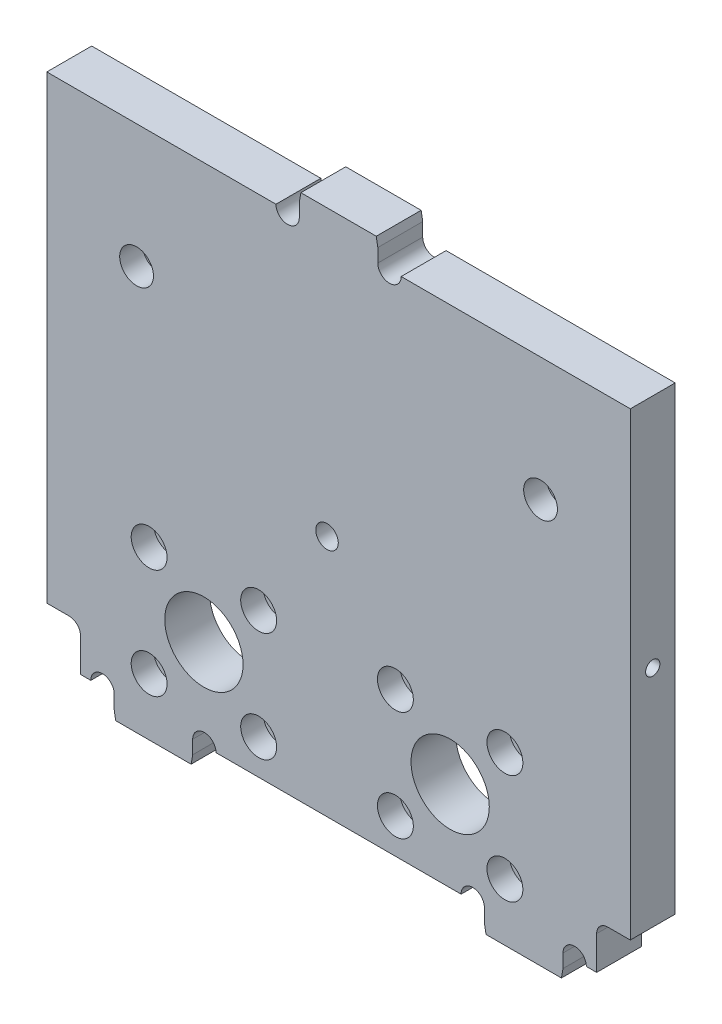
SolidWorks part; units mm, degrees
material "PE High Density"
ref_plane "Front Plane" through (0, 0, 0) normal (0, 0, 1) x (1, 0, 0)
ref_plane "Top Plane" through (0, 0, 0) normal (0, 1, 0) x (1, 0, 0)
ref_plane "Right Plane" through (0, 0, 0) normal (1, 0, 0) x (0, 0, -1)
sketch "Sketch1" plane through (0, 0, 0) normal (0, 0, 1) x (1, 0, 0)
  line L1 (-82.55, -71.4375) -> (82.55, -71.4375)
  line L2 (-82.55, -71.4375) -> (-82.55, 71.4375)
  line L3 (-82.55, 71.4375) -> (82.55, 71.4375)
  line L4 (82.55, -71.4375) -> (82.55, 71.4375)
  line L5 (-82.55, -71.4375) -> (82.55, 71.4375) construction
  line L6 (-82.55, 71.4375) -> (82.55, -71.4375) construction
  point P0 (0, 0)
  dimension "D1" = 165.1
  dimension "D2" = 142.875
extrude "Boss-Extrude1" add sketch "Sketch1" along normal blind 12.7
sketch "Sketch2" plane through (0, 0, 12.7) normal (0, 0, 1) x (1, 0, 0)
  line L0 (82.55, 71.4375) -> (-82.55, 71.4375) construction
  line L1 (-11.1125, 71.4375) -> (11.1125, 71.4375)
  line L2 (-11.1125, 71.4375) -> (-11.1125, 75.2475)
  line L3 (-10.6646, 77.7875) -> (10.6646, 77.7875)
  line L4 (11.1125, 71.4375) -> (11.1125, 75.2475)
  line L5 (10.6646, 77.7875) -> (11.1125, 75.2475)
  line L6 (-10.6646, 77.7875) -> (-11.1125, 75.2475)
  line L7 (82.55, -71.4375) -> (82.55, 71.4375) construction
  point P6 (0, 77.7875)
  dimension "D3" = 170
  dimension "D4" = 170
  dimension "D5" = 3.81
  dimension "D1" = 71.4375
  dimension "D2" = 6.35
extrude "Boss-Extrude2" add sketch "Sketch2" against normal up to surface (12.7 mm away) up to face at (0, 0, 0)
sketch "Sketch4" plane through (0, 0, 12.7) normal (0, 0, 1) x (1, 0, 0)
  line L0 (-11.1125, 71.4375) -> (-82.55, 71.4375) construction
  line L1 (-11.1125, 75.2475) -> (-11.1125, 71.4375) construction
  line L2 (-82.55, 71.4375) -> (82.55, 71.4375) construction
  line L3 (0, 77.7875) -> (0, 0) construction
  line L4 (10.6646, 77.7875) -> (-10.6646, 77.7875) construction
  line L5 (-17.7165, 71.4375) -> (-11.1125, 71.4375)
  line L6 (11.1125, 71.4375) -> (17.7165, 71.4375)
  arc A0 (-17.7165, 71.4375) -> (-11.1125, 71.4375) centre (-14.4145, 71.4375) ccw
  arc A1 (17.7165, 71.4375) -> (11.1125, 71.4375) centre (14.4145, 71.4375) cw
  dimension "D1" = 6.604
  dimension "D2" = 3.302
extrude "Cut-Extrude1" cut sketch "Sketch4" against normal up to next contours A1 L6 | A0 L5
sketch "Sketch5" plane through (0, 0, 12.7) normal (0, 0, 1) x (1, 0, 0)
  line L0 (-82.55, -71.4375) -> (82.55, -71.4375) construction
  line L1 (63.5, -71.4375) -> (41.275, -71.4375)
  line L2 (63.5, -71.4375) -> (63.5, -75.2475)
  line L3 (63.0521, -77.7875) -> (41.7229, -77.7875)
  line L4 (41.275, -71.4375) -> (41.275, -75.2475)
  line L5 (82.55, -71.4375) -> (82.55, 71.4375) construction
  line L6 (41.275, -75.2475) -> (41.7229, -77.7875)
  line L7 (63.5, -75.2475) -> (63.0521, -77.7875)
  dimension "D1" = 22.225
  dimension "D2" = 6.35
  dimension "D3" = 19.05
  dimension "D4" = 170
  dimension "D5" = 170
  dimension "D6" = 3.81
extrude "Boss-Extrude3" add sketch "Sketch5" against normal up to surface (12.7 mm away) up to face at (0, 48.768, 0)
hole_wizard "#21 (0.159) Diameter Hole2" positions "Sketch32" profile "Sketch33" hole size "#21" standard "ANSI Inch"
sketch "Sketch32" plane through (82.55, 0, 0) normal (1, 0, 0) x (0, 0, -1)
  line L0 (-12.7, -71.4375) -> (0, -71.4375) construction
  point P0 (-6.35, 4.7625)
  point P5 (-6.35, -71.4375)
  dimension "D1" = 76.2
sketch "Sketch33" plane through (82.55, 4.7625, 6.35) normal (0, 1, 0) x (0, 0, -1)
  line L0 (0, 0) -> (0, 23.4383)
  line L1 (0, 23.4383) -> (2.0193, 22.225)
  line L2 (2.0193, 22.225) -> (2.0193, 0)
  line L5 (2.0193, 0) -> (0, 0)
  line L10 (0, 23.4383) -> (-2.0193, 22.225) construction
  line L11 (0, -6.35) -> (0, 107.95) construction
  dimension "Hole Dia." = 4.0386
  dimension "Hole Depth" = 22.225
  dimension "Drill Angle" = 118
hole_wizard "#21 (0.159) Diameter Hole3" positions "Sketch34" profile "Sketch35" hole size "#21" standard "ANSI Inch"
sketch "Sketch34" plane through (-82.55, 0, 0) normal (-1, 0, 0) x (0, 0, 1)
  point P0 (6.35, 4.7625)
sketch "Sketch35" plane through (-82.55, 4.7625, 6.35) normal (0, 1, 0) x (0, 0, 1)
  line L0 (0, 0) -> (0, 23.4383)
  line L1 (0, 23.4383) -> (2.0193, 22.225)
  line L2 (2.0193, 22.225) -> (2.0193, 0)
  line L5 (2.0193, 0) -> (0, 0)
  line L10 (0, 23.4383) -> (-2.0193, 22.225) construction
  line L11 (0, -6.35) -> (0, 107.95) construction
  dimension "Hole Dia." = 4.0386
  dimension "Hole Depth" = 22.225
  dimension "Drill Angle" = 118
sketch "Sketch6" plane through (0, 0, 12.7) normal (0, 0, 1) x (1, 0, 0)
  line L0 (-82.55, -71.4375) -> (41.275, -71.4375) construction
  line L1 (82.55, -71.4375) -> (0, -71.4375) construction
  line L2 (34.671, -71.4375) -> (41.275, -71.4375)
  line L3 (52.3875, -77.7875) -> (52.3875, 71.4375) construction
  line L4 (41.7229, -77.7875) -> (63.0521, -77.7875) construction
  line L5 (82.55, 71.4375) -> (17.7165, 71.4375) construction
  line L6 (63.5, -71.4375) -> (70.104, -71.4375)
  arc A0 (41.275, -71.4375) -> (34.671, -71.4375) centre (37.973, -71.4375) ccw
  arc A1 (63.5, -71.4375) -> (70.104, -71.4375) centre (66.802, -71.4375) cw
  dimension "D1" = 6.604
  dimension "D2" = 3.302
extrude "Cut-Extrude2" cut sketch "Sketch6" against normal up to surface (12.7 mm away) up to face at (17.4625, 7.5706, 0)
mirror "Mirror1" about plane through (0, 0, 0) normal (1, 0, 0) of "Boss-Extrude3", "Cut-Extrude2"
sketch "Sketch21" plane through (0, 0, 12.7) normal (0, 0, 1) x (1, 0, 0)
  line L1 (-82.55, 71.4375) -> (-82.55, -71.4375) construction
  line L2 (-34.671, -71.4375) -> (34.671, -71.4375) construction
  line L3 (-82.55, -71.4375) -> (-70.104, -71.4375) construction
  line L4 (-53.594, -30.5435) -> (-22.606, -30.5435) construction
  line L5 (-53.594, -30.5435) -> (-53.594, -61.5315) construction
  line L6 (-53.594, -61.5315) -> (-22.606, -61.5315) construction
  line L7 (-22.606, -30.5435) -> (-22.606, -61.5315) construction
  line L8 (16.0799, -30.5435) -> (47.0679, -30.5435) construction
  line L9 (16.0799, -30.5435) -> (16.0799, -61.5315) construction
  line L10 (16.0799, -61.5315) -> (47.0679, -61.5315) construction
  line L11 (47.0679, -30.5435) -> (47.0679, -61.5315) construction
  circle A0 centre (-57.15, 36.5125) radius 4.7752
  circle A1 centre (57.15, 36.5125) radius 4.7752
  circle A2 centre (-57.15, 36.5125) radius 114.3 construction
  circle A3 centre (-57.15, 36.5125) radius 66.675 construction
  circle A4 centre (-3.263, -2.7527) radius 3.1877
  circle A5 centre (-3.263, -2.7527) radius 55.5625 construction
  circle A6 centre (-38.1, -46.0375) radius 11.0754
  circle A7 centre (31.5739, -46.0375) radius 11.0754
  circle A8 centre (-38.1, -46.0375) radius 21.9118 construction
  circle A9 centre (-53.594, -30.5435) radius 5.08
  circle A10 centre (-22.606, -30.5435) radius 5.08
  circle A11 centre (-22.606, -61.5315) radius 5.08
  circle A12 centre (-53.594, -61.5315) radius 5.08
  circle A13 centre (31.5739, -46.0375) radius 21.9118 construction
  circle A14 centre (16.0799, -30.5435) radius 5.08
  circle A15 centre (47.0679, -30.5435) radius 5.08
  circle A16 centre (47.0679, -61.5315) radius 5.08
  circle A17 centre (16.0799, -61.5315) radius 5.08
  dimension "D1" = 228.6
  dimension "D3" = 9.5504
  dimension "D4" = 9.5504
  dimension "D6" = 133.35
  dimension "D7" = 6.3754
  dimension "D8" = 111.125
  dimension "D9" = 22.1508
  dimension "D10" = 22.1508
  dimension "D15" = 10.16
  dimension "D5" = 25.4
  dimension "D11" = 25.4
  dimension "D12" = 44.45
  dimension "D13" = 30.988
  dimension "D14" = 30.988
  dimension "D16" = 30.988
  dimension "D2" = 107.95
extrude "Cut-Extrude10" cut sketch "Sketch21" against normal blind 6.35 contours A12 | A0 | A9 | A10 | A11 | A6 | A4 | A7 | A14 | A15 | A16 | A17 | A1 region at (-53.594, -61.5315, 12.7)
hole_wizard "#8 Clearance Hole1" positions "Sketch22" profile "Sketch23" hole size "#8" standard "ANSI Inch"
sketch "Sketch22" plane through (0, 0, 12.7) normal (0, 0, 1) x (1, 0, 0)
  point P0 (-57.15, 36.5125)
  point P3 (57.15, 36.5125)
  point P6 (-3.263, -2.7527)
sketch "Sketch23" plane through (-57.15, 36.5125, 12.7) normal (1, 0, 0) x (0, -1, 0)
  line L0 (0, 0) -> (0, 20.4007)
  line L1 (0, 20.4007) -> (2.2479, 19.05)
  line L2 (2.2479, 19.05) -> (2.2479, 0)
  line L5 (2.2479, 0) -> (0, 0)
  line L10 (0, 20.4007) -> (-2.2479, 19.05) construction
  line L11 (0, -6.35) -> (0, 107.95) construction
  dimension "Hole Dia." = 4.4958
  dimension "Hole Depth" = 19.05
  dimension "Drill Angle" = 118
hole_wizard "M3 Clearance Hole1" positions "Sketch24" profile "Sketch25" hole size "M3" standard "ANSI Metric"
sketch "Sketch24" plane through (0, 0, 12.7) normal (0, 0, 1) x (1, 0, 0)
  point P0 (-53.594, -30.5435)
  point P3 (-22.606, -30.5435)
  point P6 (-22.606, -61.5315)
  point P9 (-53.594, -61.5315)
  point P12 (16.0799, -61.5315)
  point P15 (16.0799, -30.5435)
  point P18 (47.0679, -30.5435)
  point P21 (47.0679, -61.5315)
  point P24 (-53.6, -30.5375)
sketch "Sketch25" plane through (-53.594, -30.5435, 12.7) normal (1, 0, 0) x (0, -1, 0)
  line L0 (0, 0) -> (0, 20.0715)
  line L1 (0, 20.0715) -> (1.7, 19.05)
  line L2 (1.7, 19.05) -> (1.7, 0)
  line L5 (1.7, 0) -> (0, 0)
  line L10 (0, 20.0715) -> (-1.7, 19.05) construction
  line L11 (0, -6.35) -> (0, 107.95) construction
  dimension "Hole Dia." = 3.4
  dimension "Hole Depth" = 19.05
  dimension "Drill Angle" = 118
sketch "Sketch28" plane through (0, 0, 12.7) normal (0, 0, 1) x (1, 0, 0)
  circle A2 centre (31.5739, -46.0375) radius 11.0754 construction
  circle A3 centre (-38.1, -46.0375) radius 11.0754 construction
  circle A4 centre (31.5739, -46.0375) radius 11.0754
  circle A5 centre (-38.1, -46.0375) radius 11.0754
extrude "Cut-Extrude11" cut sketch "Sketch28" against normal up to surface (12.7 mm away) up to face at (-55.294, -30.5435, 0)
sketch "Sketch29" plane through (0, 0, 12.7) normal (0, 0, 1) x (1, 0, 0)
  line L1 (-82.55, -71.4375) -> (-73.025, -71.4375)
  line L2 (-82.55, -71.4375) -> (-82.55, -58.7375)
  line L3 (-82.55, -58.7375) -> (-73.025, -58.7375)
  line L4 (-73.025, -71.4375) -> (-73.025, -58.7375)
  line L5 (82.55, -71.4375) -> (73.025, -71.4375)
  line L6 (82.55, -71.4375) -> (82.55, -58.7375)
  line L7 (82.55, -58.7375) -> (73.025, -58.7375)
  line L8 (73.025, -71.4375) -> (73.025, -58.7375)
  dimension "D1" = 12.7
  dimension "D2" = 9.525
extrude "Cut-Extrude12" cut sketch "Sketch29" against normal through all
fillet "Fillet1" radius 3.175 2 edges at (73.025, -58.7375, 6.35) (-73.025, -58.7375, 6.35)
equation "\"D4@Sketch2\"=\"D3@Sketch2\""
equation "\"D2@Sketch4\"=\"D1@Sketch4\"/2"
equation "\"D2@Sketch6\"=\"D1@Sketch6\"/2"
equation "\"D4@Sketch21\"=\"D3@Sketch21\""
equation "\"D5@Sketch21\"=(6.5-\"D1@Sketch21\"/2)/2"
equation "\"D6@Sketch21\"=4.5+.75"
equation "\"D8@Sketch21\"=4+.375"
equation "\"D9@Sketch21\"=22.1mm+.002"
equation "\"D10@Sketch21\"=\"D9@Sketch21\""
equation "\"D14@Sketch21\"=\"D13@Sketch21\""
equation "\"D16@Sketch21\"=\"D13@Sketch21\""
equation "\"D2@Sketch1\"=6.000in-.375"
